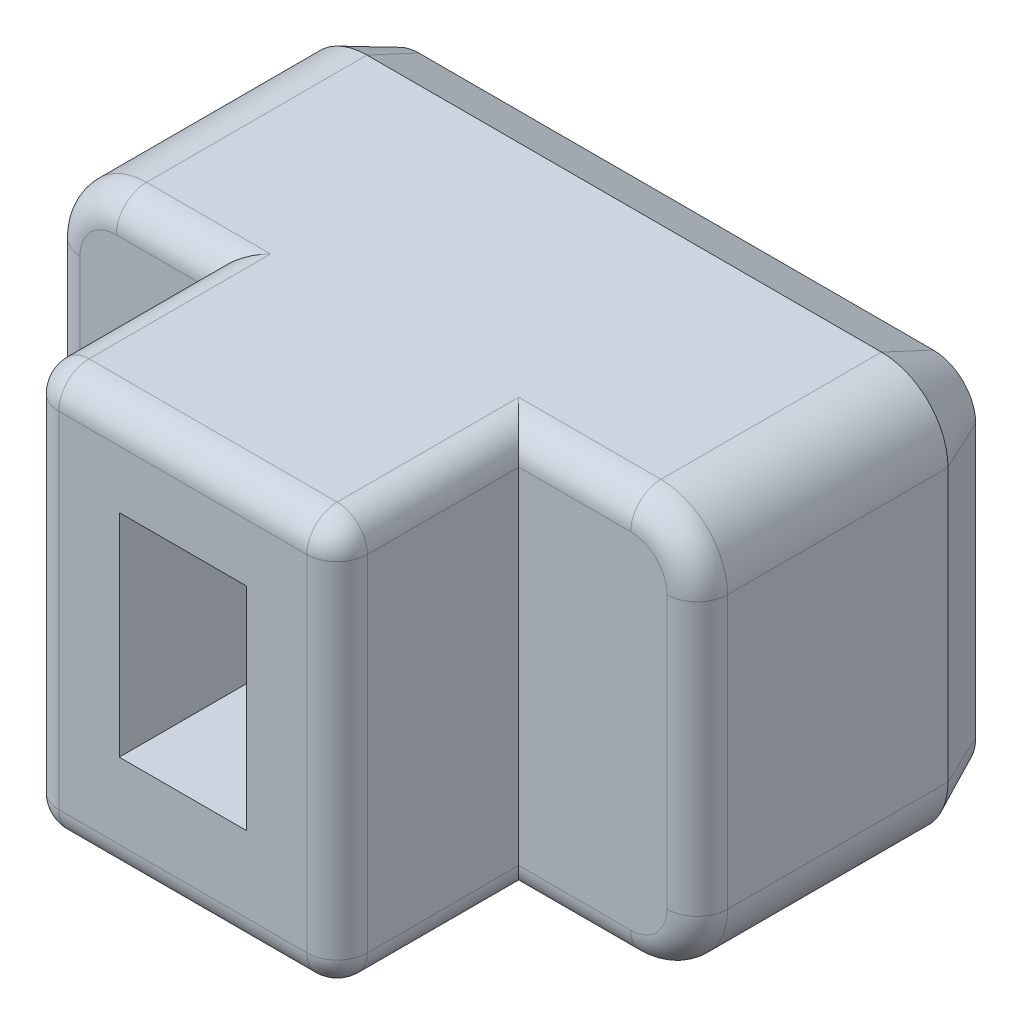
SolidWorks part; units mm, degrees
ref_plane "Plan de face" through (0, 0, 0) normal (0, 0, 1) x (1, 0, 0)
ref_plane "Plan de dessus" through (0, 0, 0) normal (0, 1, 0) x (1, 0, 0)
ref_plane "Plan de droite" through (0, 0, 0) normal (1, 0, 0) x (0, 0, -1)
sketch "Esquisse2" plane through (0, 0, 0) normal (0, 0, 1) x (1, 0, 0)
  line L1 (1.1, 0) -> (9.6, 0)
  line L2 (0, 1.1) -> (0, 5.6)
  line L3 (1.1, 6.7) -> (9.6, 6.7)
  line L4 (10.7, 1.1) -> (10.7, 5.6)
  arc A0 (9.6, 6.7) -> (10.7, 5.6) centre (9.6, 5.6) cw
  arc A1 (9.6, 0) -> (10.7, 1.1) centre (9.6, 1.1) ccw
  arc A2 (1.1, 0) -> (0, 1.1) centre (1.1, 1.1) cw
  arc A3 (0, 5.6) -> (1.1, 6.7) centre (1.1, 5.6) cw
  point P7 (10.7, 6.7)
  point P12 (0, 0)
  point P15 (0, 6.7)
  dimension "D3" = 1.1
  dimension "D1" = 10.7
  dimension "D2" = 6.7
extrude "Boss.-Extru.1" add sketch "Esquisse2" along normal blind 8
sketch "Esquisse3" plane through (0, 0, 8) normal (0, 0, 1) x (1, 0, 0)
  line L0 (0, 5.6) -> (0, 1.1) construction
  line L1 (4.15, 5.25) -> (6.25, 5.25)
  line L2 (4.15, 5.25) -> (4.15, 1.75)
  line L3 (4.15, 1.75) -> (6.25, 1.75)
  line L4 (6.25, 5.25) -> (6.25, 1.75)
  line L5 (10.7, 1.1) -> (10.7, 5.6) construction
  line L6 (9.6, 6.7) -> (1.1, 6.7) construction
  line L7 (1.1, 0) -> (9.6, 0) construction
  dimension "D1" = 2.1
  dimension "D2" = 3.5
  dimension "D3" = 4.15
  dimension "D4" = 4.45
  dimension "D5" = 1.45
  dimension "D6" = 1.75
extrude "Enlèv. mat.-Extru.1" cut sketch "Esquisse3" against normal blind 3
sketch "Esquisse4" plane through (0, 0, 8) normal (0, 0, 1) x (1, 0, 0)
  line L0 (2.65, 6.7) -> (2.65, 0)
  line L1 (9.6, 6.7) -> (1.1, 6.7) construction
  line L2 (1.1, 0) -> (9.6, 0) construction
  line L3 (2.65, 0) -> (7.75, 0)
  line L4 (7.75, 0) -> (7.75, 6.7)
  line L5 (7.75, 6.7) -> (2.65, 6.7)
  line L6 (4.15, 5.25) -> (4.15, 1.75) construction
  line L7 (6.25, 1.75) -> (6.25, 5.25) construction
  dimension "D1" = 1.5
  dimension "D2" = 1.5
extrude "Enlèv. mat.-Extru.2" cut sketch "Esquisse4" against normal blind 3 flip side to cut
fillet "Congé1" radius 0.5 18 edges at (8.675, 0, 5) (10.3778, 0.3222, 5) (10.7, 3.35, 5) (10.3778, 6.3778, 5) (1.875, 6.7, 5) (0.3222, 6.3778, 5) (1.875, 0, 5) (0.3222, 0.3222, 5) (7.75, 6.7, 6.5) (2.65, 6.7, 6.5) (7.75, 0, 6.5) (2.65, 0, 6.5) (2.65, 3.35, 8) (5.2, 6.7, 8) (7.75, 3.35, 8) (5.2, 0, 8) (8.675, 6.7, 5) (0, 3.35, 5)
chamfer "Chanfrein1" distance 0.4 angle 65 8 edges at (5.35, 0, 0) (10.3778, 0.3222, 0) (0.3222, 0.3222, 0) (10.7, 3.35, 0) (0, 3.35, 0) (10.3778, 6.3778, 0) (0.3222, 6.3778, 0) (5.35, 6.7, 0) first distance on face at (5.35, 3.35, 0)
ref_plane "Plan1" through (0, 0, 0.2) normal (0, 0, 1) x (1, 0, 0)
sketch "Esquisse5" plane through (0, 0, 0.2) normal (0, 0, 1) x (1, 0, 0)
  line L0 (-0.9378, 5.0686) -> (11.6517, 5.0686) construction
  text T0 "BARO" font "Century Gothic" height 3.5
extrude "Enlèv. mat.-Extru.3" cut sketch "Esquisse5" against normal blind 0.3
extrude "Boss.-Extru.2" add sketch "Esquisse5<3>" against normal blind 0.2 from offset 0.2 offset against normal yes
sketch "Esquisse5<3>" plane through (0, 0, 0.2) normal (0, 0, 1) x (1, 0, 0) same geometry as "Esquisse5"
